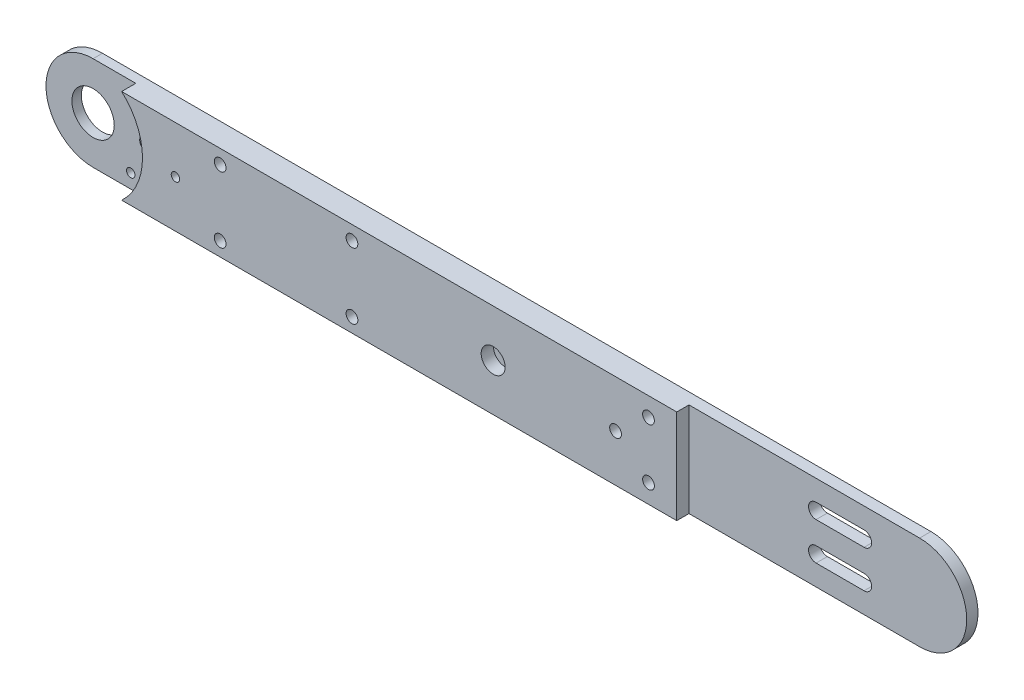
SolidWorks part; units mm, degrees
ref_plane "前视基准面" through (0, 0, 0) normal (0, 0, 1) x (1, 0, 0)
ref_plane "上视基准面" through (0, 0, 0) normal (0, 1, 0) x (1, 0, 0)
ref_plane "右视基准面" through (0, 0, 0) normal (1, 0, 0) x (0, 0, -1)
other "Configuration Table"
sketch "草图1" plane through (0, 0, 0) normal (0, 0, 1) x (1, 0, 0)
  line L0 (0, 0) -> (176, 0) construction
  line L5 (0, 10) -> (176, 10)
  line L6 (0, 10) -> (0, -10)
  line L7 (0, -10) -> (176, -10)
  line L8 (176, 10) -> (176, -10)
  circle A2 centre (0, 0) radius 10
  circle A5 centre (88, 0) radius 2.55
  circle A8 centre (88, 0) radius 1.1
  circle A9 centre (0, 0) radius 2.55
  circle A10 centre (0, 0) radius 1.1
  circle A11 centre (176, 0) radius 10
  dimension "D1" = 20
  dimension "D2" = 176
  dimension "D4" = 2.2
  dimension "D5" = 5.1
  dimension "D3" = 176
extrude "凸台-拉伸1" add sketch "草图1" along normal blind 5 contours A2 | L7 L8 L5 L6 | A11
extrude "切除-拉伸2" cut sketch "草图1<3>" along normal through all contours A10 | A8
sketch "草图1<3>" plane through (0, 0, 0) normal (0, 0, 1) x (1, 0, 0) same geometry as "草图1"
extrude "切除-拉伸3" cut sketch "草图1<4>" along normal blind 2.6 contours A5 | A9
sketch "草图1<4>" plane through (0, 0, 0) normal (0, 0, 1) x (1, 0, 0) same geometry as "草图1"
sketch "草图2" plane through (0, 0, 0) normal (0, 0, -1) x (-1, 0, 0)
  line L0 (0, -10) -> (-176, -10) construction
  line L1 (0, 10) -> (-176, 10) construction
  line L2 (-121, 6) -> (-121, -6) construction
  circle A0 centre (-121, -6) radius 1.25
  circle A1 centre (-121, 6) radius 1.25
  circle A2 centre (-121, -6) radius 2
  circle A3 centre (-121, 6) radius 2
  circle A4 centre (-88, 0) radius 1.1 construction
  circle A5 centre (-114, 0) radius 2
  circle A6 centre (-114, 0) radius 1.25
  circle A7 centre (-58, 7) radius 1.25
  circle A9 centre (-58, 7) radius 2
  circle A10 centre (-30, 7) radius 2
  circle A11 centre (-30, 7) radius 1.25
  circle A12 centre (-58, -7) radius 2
  circle A13 centre (-58, -7) radius 1.25
  circle A14 centre (-30, -7) radius 1.25
  circle A15 centre (-30, -7) radius 2
  point P16 (-121, 0)
  dimension "D1" = 4
  dimension "D2" = 2.5
  dimension "D3" = 33
  dimension "D4" = 4
  dimension "D5" = 4
  dimension "D6" = 7
  dimension "D7" = 30
  dimension "D8" = 30
  dimension "D9" = 3
  dimension "D10" = 3
extrude "切除-拉伸4" cut sketch "草图2" against normal through all contours A1 | A0 | A6 | A13 | A14 | A11 | A7
extrude "切除-拉伸5" cut sketch "草图2<3>" along normal offset from surface (2.5 mm away) 2.5 from surface contours A3 | A2 | A5 | A9 | A10 | A15 | A12 up to face at (56.75, 7, 0) starting at face at (56.75, 7, 5)
sketch "草图2<3>" plane through (0, 0, 0) normal (0, 0, -1) x (-1, 0, 0) same geometry as "草图2"
sketch "草图3" plane through (0, 10, 0) normal (0, 1, 0) x (1, 0, 0)
  line L0 (0, 0) -> (176, 0) construction
  line L1 (127, 0) -> (186, 0)
  line L2 (127, 0) -> (127, -2.6)
  line L3 (127, -2.6) -> (186, -2.6)
  line L4 (186, 0) -> (186, -2.6)
  dimension "D1" = 59
  dimension "D2" = 2.6
extrude "切除-拉伸6" cut sketch "草图3" against normal through all
sketch "草图4" plane through (0, 0, 5) normal (0, 0, 1) x (1, 0, 0)
  line L0 (164.2, -2.4) -> (154, -2.4)
  line L5 (164.2, -2.4) -> (164.2, -5.6)
  line L6 (164.2, -5.6) -> (154, -5.6)
  line L7 (154, -2.4) -> (154, -5.6)
  line L8 (164.2, 5.6) -> (154, 5.6)
  line L9 (164.2, 5.6) -> (164.2, 2.4)
  line L10 (164.2, 2.4) -> (154, 2.4)
  line L11 (154, 5.6) -> (154, 2.4)
  line L12 (154, 4) -> (154, -4)
  line L13 (186, 0) -> (154, 0)
  circle A3 centre (164.2, -4) radius 1.6
  circle A4 centre (154, -4) radius 1.6
  circle A5 centre (164.2, 4) radius 1.6
  circle A6 centre (154, 4) radius 1.6
  arc A7 (176, -10) -> (176, 10) centre (176, 0) ccw construction
  dimension "D1" = 10.2
  dimension "D3" = 3.2
  dimension "D4" = 3.2
  dimension "D2" = 8
  dimension "D5" = 32
extrude "切除-拉伸7" cut sketch "草图4" against normal through all contours A6 | L10 L11 L8 L9 | A5 | L6 L7 L0 L5 | A4 | A3
mirror "镜向1" about plane through (0, 0, 0) normal (0, 0, 1) of bodies 153
sketch "草图5" plane through (0, 0, 0) normal (0, 0, 1) x (1, 0, 0)
  line L1 (-19.6603, 11.6004) -> (191.1829, 11.6004)
  line L2 (-19.6603, 11.6004) -> (-19.6603, -13.6356)
  line L3 (-19.6603, -13.6356) -> (191.1829, -13.6356)
  line L4 (191.1829, 11.6004) -> (191.1829, -13.6356)
extrude "切除-拉伸8" cut sketch "草图5" along normal through all
sketch "草图6" plane through (0, 0, 0) normal (0, 0, 1) x (1, 0, 0)
  circle A0 centre (0, 0) radius 13.5
  dimension "D1" = 27
extrude "切除-拉伸9" cut sketch "草图6" against normal blind 3
sketch "草图7" plane through (0, 0, -5) normal (0, 0, -1) x (-1, 0, 0)
  circle A0 centre (0, 0) radius 4.5
  dimension "D1" = 9
extrude "切除-拉伸10" cut sketch "草图7" against normal through all
sketch "草图8" plane through (0, 0, -5) normal (0, 0, -1) x (-1, 0, 0)
  line L0 (0, 10) -> (-176, 10) construction
  line L1 (0, -10) -> (-176, -10) construction
  circle A0 centre (-11.5, 0) radius 1.6
  circle A1 centre (-8, 7) radius 0.9
  circle A2 centre (-8, -7) radius 0.9
  circle A3 centre (-20.5, 0) radius 0.9
  dimension "D2" = 3.2
  dimension "D3" = 1.8
  dimension "D1" = 11.5
  dimension "D4" = 3
  dimension "D5" = 3
  dimension "D6" = 8
  dimension "D7" = 12.5
extrude "切除-拉伸11" cut sketch "草图8" against normal through all
